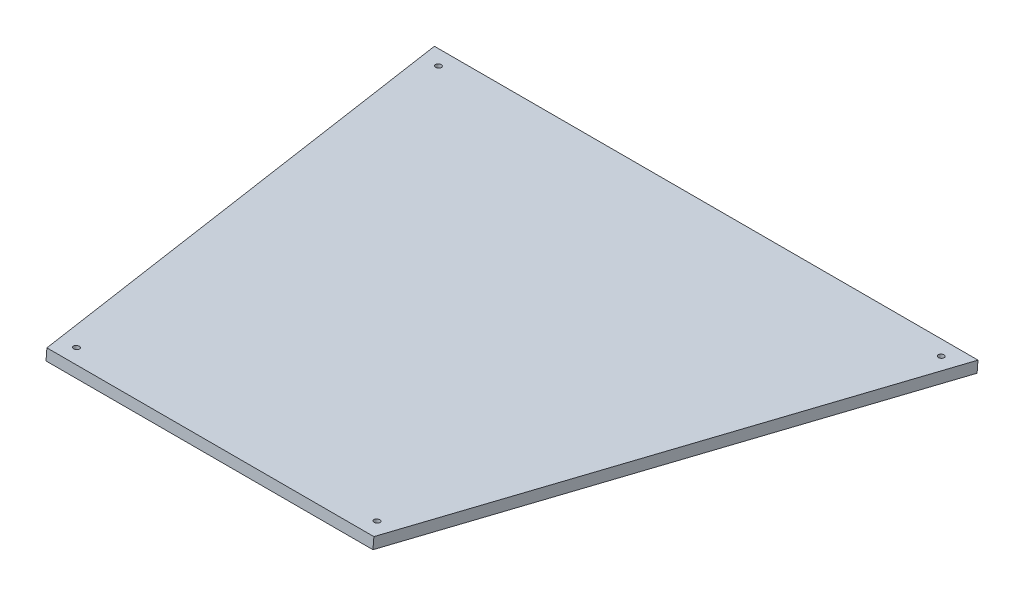
SolidWorks part; units mm, degrees
ref_plane "Front Plane" through (0, 0, 0) normal (0, 0, 1) x (1, 0, 0)
ref_plane "Top Plane" through (0, 0, 0) normal (0, 1, 0) x (1, 0, 0)
ref_plane "Right Plane" through (0, 0, 0) normal (1, 0, 0) x (0, 0, -1)
ref_plane "Plane1" through (-0.001, -12330.8848, 1017.2175) normal (0, -0.9966, 0.0822) x (-1, 0, 0)
sketch "Sketch1" plane through (-0.001, -12330.8848, 1017.2175) normal (0, -0.9966, 0.0822) x (-1, 0, 0)
  line L0 (927.9324, -1893.2884) -> (1306.8393, -1893.2884)
  line L1 (1306.8393, -1893.2884) -> (1432.3521, -1316.7398)
  line L2 (1432.3521, -1316.7398) -> (802.4196, -1316.7398)
  line L3 (802.4196, -1316.7398) -> (927.9324, -1893.2884)
  line L4 (802.4183, -1316.7398) -> (1432.3534, -1316.7398) construction
  line L5 (928.076, -1893.948) -> (801.0629, -1310.5075) construction
  line L6 (1433.7088, -1310.5075) -> (1306.6957, -1893.948) construction
  line L7 (1306.8419, -1893.2884) -> (927.9298, -1893.2884) construction
extrude "Boss-Extrude1" add sketch "Sketch1" along normal blind 12.7
sketch "Sketch2" plane through (-0.001, -12330.8848, 1017.2175) normal (0, 0.9966, -0.0822) x (1, 0, 0)
  circle A5 centre (-1291.4903, -1874.249) radius 3.2639
  circle A7 centre (-1291.4903, -1874.249) radius 3.2639
  circle A8 centre (-943.2814, -1874.249) radius 3.2639
  circle A9 centre (-943.2814, -1874.249) radius 3.2639
  circle A10 centre (-826.063, -1335.8007) radius 3.2639
  circle A11 centre (-826.063, -1335.8007) radius 3.2639
  circle A12 centre (-1408.7087, -1335.8007) radius 3.2639
  circle A13 centre (-1408.7087, -1335.8007) radius 3.2639
  point P16 (-1397.9593, -1360.7012)
  dimension "D7" = 0
  dimension "D8" = 0
  dimension "D9" = 0
  dimension "D13" = 0
extrude "Cut-Extrude1" cut sketch "Sketch2" against normal through all
